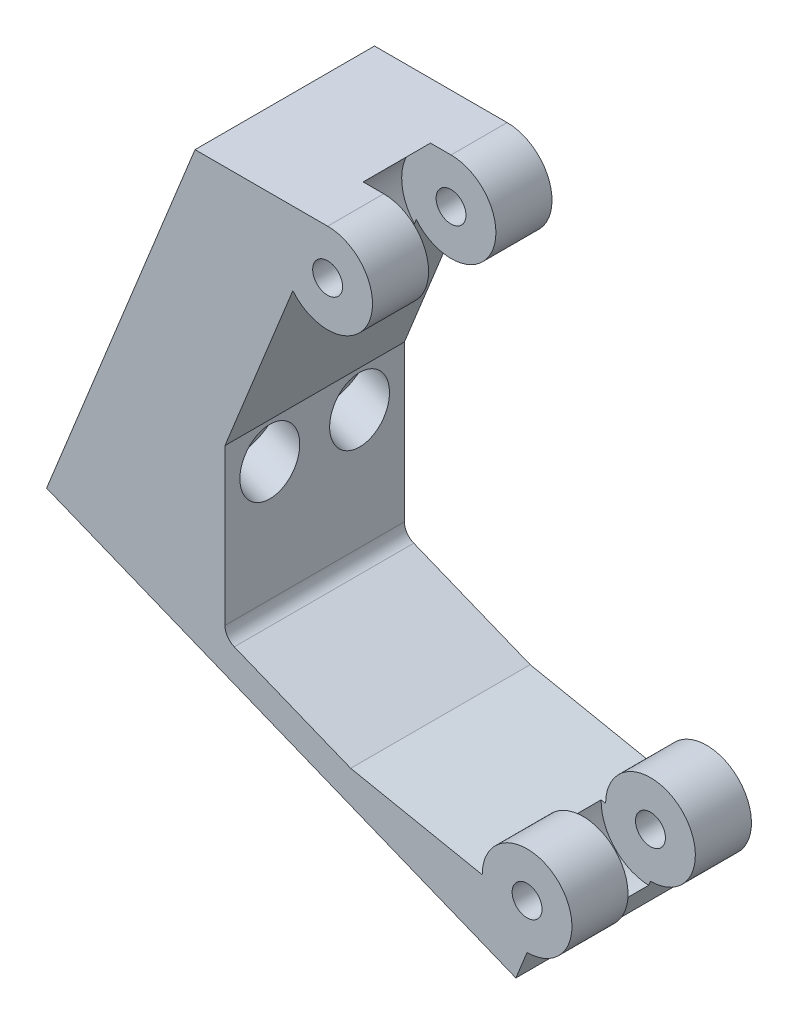
SolidWorks part; units mm, degrees
other "Markup1"
sketch "Sketch3" plane through (0, 0, 12) normal (0, 0, 1) x (1, 0, 0)
other "DetailItem1"
other "DetailItem3"
other "DetailItem5"
ref_plane "Front Plane" through (0, 0, 0) normal (0, 0, 1) x (1, 0, 0)
ref_plane "Top Plane" through (0, 0, 0) normal (0, 1, 0) x (1, 0, 0)
ref_plane "Right Plane" through (0, 0, 0) normal (1, 0, 0) x (0, 0, -1)
sketch "Sketch1" plane through (0, 0, 0) normal (0, 0, 1) x (1, 0, 0)
  line L2 (0, 6.6407) -> (0, 35.2105)
  line L3 (0, 35.2105) -> (8.8654, 35.2105)
  line L5 (6.5411, 30.3139) -> (2, 19.0743)
  line L6 (2, 19.0743) -> (2, 7.9897)
  line L7 (10.4069, 4.5931) -> (19.1992, 2.8287)
  line L11 (8.8654, 32.2105) -> (22.1992, 2.8287) construction
  line L15 (8.8654, 32.2105) -> (8.8654, 4.9405) construction
  line L16 (8.8654, 4.9405) -> (22.1992, 2.8287) construction
  line L17 (8.8654, 4.9405) -> (8.8654, -11.9834) construction
  line L21 (2, 7.9897) -> (10.4069, 4.5931)
  line L22 (-988.4786, -0.1713) -> (16.8603, -0.1713) construction
  line L23 (0, 6.6407) -> (21.45, -2.0257)
  line L24 (-905.7338, 372.5809) -> (46380.6427, -18732.3554) construction
  line L25 (22.1992, -0.1713) -> (50022.1992, -0.1713) construction
  line L26 (22.1992, -0.1713) -> (21.45, -2.0257)
  line L27 (-904.9846, 374.4353) -> (46381.392, -18730.501) construction
  line L28 (0.4221, 6.4701) -> (-46358.7706, 18736.7998) construction
  line L29 (2, 19.0743) -> (18732.3297, 46378.267) construction
  arc A0 (22.1992, -0.1713) -> (19.1992, 2.8287) centre (22.1992, 2.8287) ccw
  arc A1 (8.8654, 35.2105) -> (6.5411, 30.3139) centre (8.8654, 32.2105) cw
  circle A2 centre (8.8654, 32.2105) radius 1
  circle A3 centre (22.1992, 2.8287) radius 1
  point P2 (0, 0)
  dimension "D1" = 2
  dimension "D3" = 3
  dimension "D4" = 27.27
  dimension "D5" = 13.5
  dimension "D8" = 81
  dimension "D12" = 22
  dimension "D2" = 2
  dimension "D9" = 90
  dimension "D13" = 2
extrude "Boss-Extrude1" add sketch "Sketch1" along normal blind 12
ref_plane "midplane" through (0, 0, 6) normal (0, 0, 1) x (1, 0, 0)
sketch "Sketch2" plane through (0, 0, 6) normal (0, 0, 1) x (1, 0, 0)
  circle A0 centre (8.8654, 32.2105) radius 3.3
  circle A1 centre (22.1992, 2.8287) radius 3.3
  dimension "D1" = 6.6
extrude "Cut-Extrude1" cut sketch "Sketch2" against normal blind 2.25 and the other way blind 2.25
fillet "Fillet3" radius 1 1 edges at (2, 7.9897, 6)
ref_plane "Plane1" through (2.3065, 5.7088, 0) normal (-0.3746, -0.9272, 0) x (-0.9272, 0.3746, 0)
ref_plane "Plane2" through (-12.2296, 4.9411, 0) normal (-0.9272, 0.3746, 0) x (0, 0, -1)
sketch "Sketch4" plane through (-12.2296, 4.9411, 0) normal (-0.9272, 0.3746, 0) x (0, 0, -1)
  line L0 (6.6, -6.1571) -> (-6.6, -6.1571) construction
  line L1 (-12, -32.6466) -> (0, -32.6466)
  line L2 (-12, -32.6466) -> (-12, -6.1571)
  line L3 (-12, -6.1571) -> (0, -6.1571)
  line L4 (0, -32.6466) -> (0, -6.1571)
extrude "Boss-Extrude2" add sketch "Sketch4" against normal up to surface up to face at (0, 20.9256, 6)
sketch "Hole positions" plane through (7.6836, 33.1417, 0) normal (-0.9272, 0.3746, 0) x (0, 0, -1)
  line L0 (-12, 17.4202) -> (0, 17.4202) construction
  line L1 (-8.25, 3.3877) -> (-3.75, 3.3877) construction
  line L2 (0, 24.8243) -> (0, 15.1722) construction
  line L3 (-6, -1.7766) -> (-6, 49998.2234) construction
  line L4 (-6, 52.9241) -> (-6, 14.2895) construction
  line L5 (-12, 19.6681) -> (-12, 15.1722) construction
  line L6 (-12, 3.4206) -> (-12, 10.3547) construction
  line L7 (-12, 6.8877) -> (-6, 6.8877) construction
  circle A0 centre (-9, 17.4202) radius 1.2
  circle A1 centre (-3, 17.4202) radius 1.2
  circle A2 centre (-6, 6.8877) radius 1.2
  point P8 (-9, 17.4202)
  point P9 (-3, 17.4202)
  point P10 (-6, 6.8877)
  point P26 (0, 0)
  dimension "D2" = 2.4
  dimension "D1" = 3
  dimension "D3" = 3.5
extrude "Screw shaft holes" cut sketch "Hole positions" against normal through all both and the other way through all
sketch "Sketch5" plane through (-4.9057, 1.982, 0) normal (0.9272, -0.3746, 0) x (0, 0, -1)
  circle A0 centre (-6, 26.7191) radius 2
  circle A1 centre (-9, 16.1866) radius 2
  circle A2 centre (-3, 16.1866) radius 2
  dimension "D1" = 4
extrude "Cut-Extrude3" cut sketch "Sketch5" against normal blind 1 and the other way blind 5
equation "\"axle-diameter\"=2"
equation "\"D1@Sketch1\"=\"axle-diameter\""
equation "\"switch-thickness\"=12"
equation "\"D1@Boss-Extrude1\"=\"switch-thickness\""
equation "\"base-width\"=4.0"
equation "\"axle-bushing-radius\"=3"
equation "\"D3@Sketch1\"= \"axle-bushing-radius\""
equation "\"D1@Sketch2\"=\"axle-bushing-radius\"*2.2"
equation "\"D1@Cut-Extrude1\"=\"switch-thickness\"/6+\"clearance\""
equation "\"D2@Cut-Extrude1\"=\"switch-thickness\"/6+\"clearance\""
equation "\"clearance\"= 0.25"
equation "\"arm-width\"=3.0"
equation "\"min-diameter\"=70"
